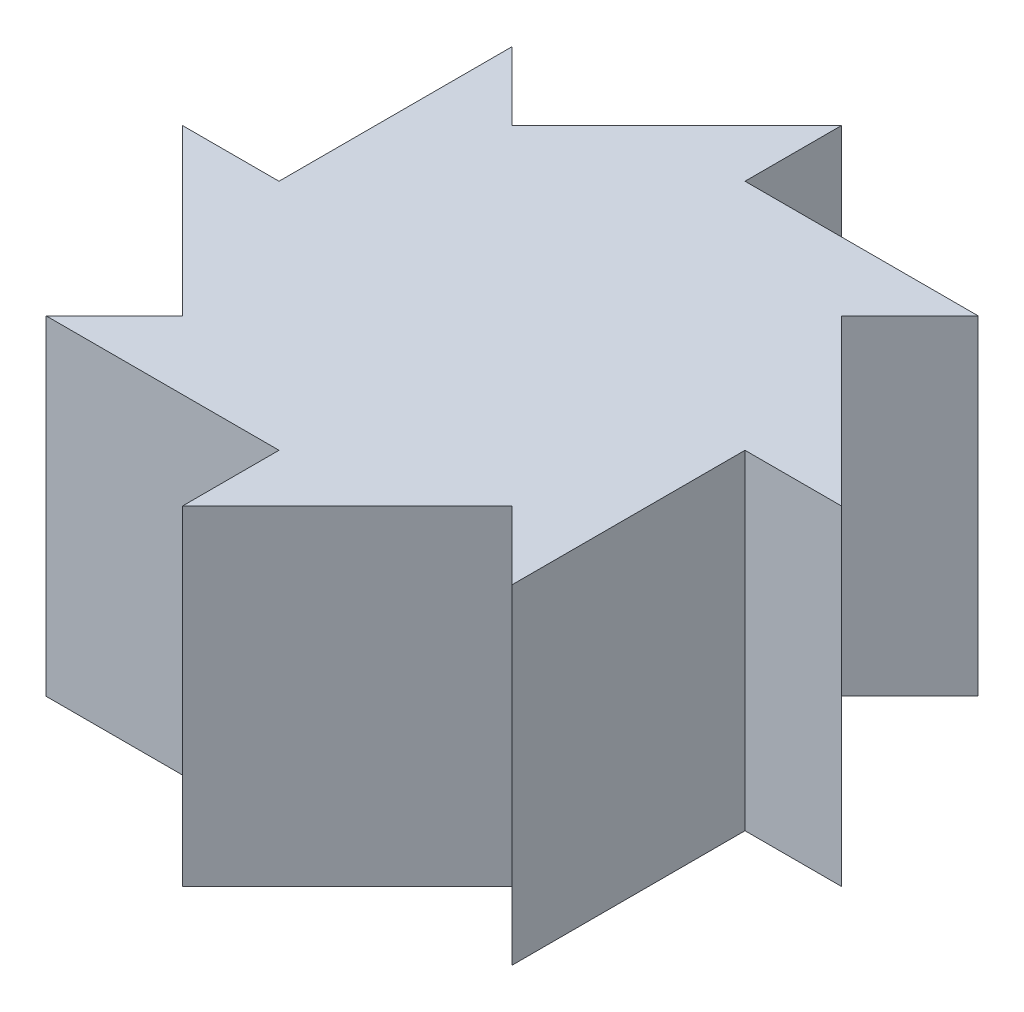
SolidWorks part; units mm, degrees
ref_plane "Front Plane" through (0, 0, 0) normal (0, 0, 1) x (1, 0, 0)
ref_plane "Top Plane" through (0, 0, 0) normal (0, 1, 0) x (1, 0, 0)
ref_plane "Right Plane" through (0, 0, 0) normal (1, 0, 0) x (0, 0, -1)
sketch "Sketch1" plane through (0, 0, 0) normal (0, 1, 0) x (1, 0, 0)
  circle A0 centre (0, 0) radius 5
  dimension "D1" = 10
extrude "Boss-Extrude1" add sketch "Sketch1" along normal blind 5
ref_point "Point1"
ref_axis "Axis2" through (0, 5, 0) along (0, 1, 0)
sketch "Sketch2" plane through (0, 5, 0) normal (0, 1, 0) x (1, 0, 0)
  line L0 (0, 0) -> (0, 5) construction
  line L1 (0, 5) -> (0, 3.5355)
  line L2 (0, 3.5355) -> (3.5355, 3.5355)
  circle A0 centre (0, 0) radius 5 construction
  arc A1 (0, 5) -> (3.5355, 3.5355) centre (0, 0) cw
extrude "Cut-Extrude1" cut sketch "Sketch2" against normal through all
pattern_circular "CirPattern1" count 8 over 360 about axis through (0, 5, 0) along (0, 1, 0) of "Cut-Extrude1"
